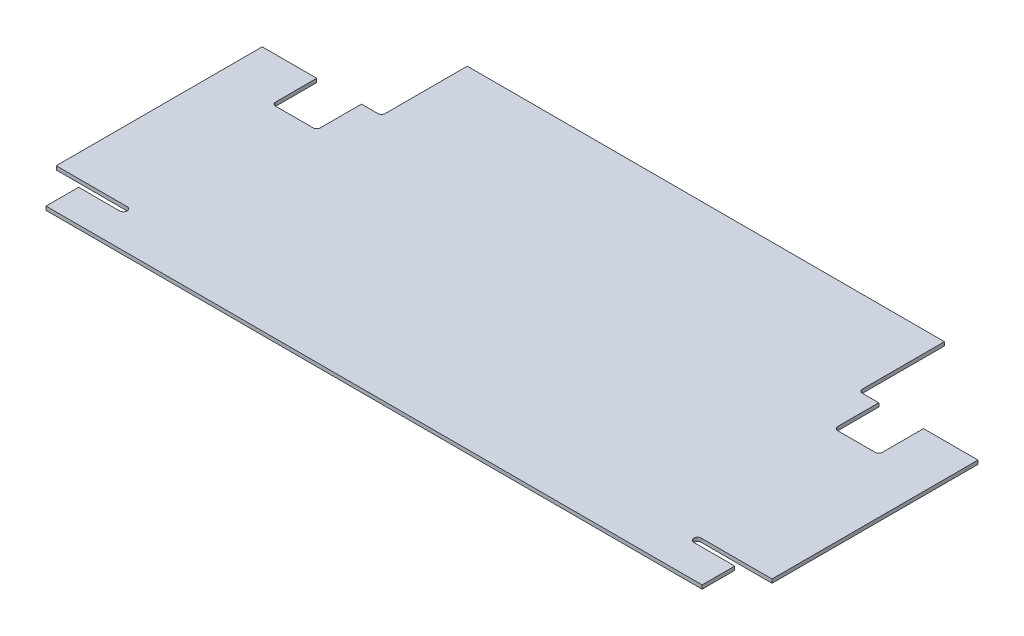
SolidWorks part; units mm, degrees
material "Acrylic (Medium-high impact)"
ref_plane "Front Plane" through (0, 0, 0) normal (0, 0, 1) x (1, 0, 0)
ref_plane "Top Plane" through (0, 0, 0) normal (0, 1, 0) x (1, 0, 0)
ref_plane "Right Plane" through (0, 0, 0) normal (1, 0, 0) x (0, 0, -1)
sketch "Sketch1" plane through (0, 0, 0) normal (0, 1, 0) x (1, 0, 0)
  line L1 (-304.8, 152.4) -> (304.8, 152.4)
  line L2 (-304.8, 152.4) -> (-304.8, -152.4)
  line L3 (-304.8, -152.4) -> (304.8, -152.4)
  line L4 (304.8, 152.4) -> (304.8, -152.4)
  line L5 (-304.8, 152.4) -> (304.8, -152.4) construction
  line L6 (-304.8, -152.4) -> (304.8, 152.4) construction
  point P0 (0, 0)
  dimension "D1" = 609.6
  dimension "D2" = 304.8
extrude "Boss-Extrude1" add sketch "Sketch1" along normal blind 3.175
sketch "Sketch3" plane through (0, 3.175, 0) normal (0, 1, 0) x (1, 0, 0)
  line L0 (-304.8, -152.4) -> (304.8, -152.4) construction
  line L1 (-304.8, 152.4) -> (304.8, 152.4)
  line L2 (-304.8, 152.4) -> (-304.8, 57.15)
  line L3 (-304.8, 57.15) -> (-203.2, 57.15)
  line L4 (-203.2, 130.175) -> (-203.2, 57.15)
  line L5 (0, 38.7483) -> (0, -39.3783) construction
  line L6 (203.2, 130.175) -> (203.2, 57.15)
  line L7 (304.8, 57.15) -> (203.2, 57.15)
  line L8 (304.8, 152.4) -> (304.8, 57.15)
  line L10 (-203.2, 130.175) -> (203.2, 130.175)
  dimension "D1" = 101.6
  dimension "D2" = 209.55
  dimension "D3" = 282.575
extrude "Cut-Extrude1" cut sketch "Sketch3" against normal up to next
fillet "Fillet1" radius 3.175 2 edges at (203.2, 1.5875, -57.15) (-203.2, 1.5875, -57.15)
sketch "Sketch4" plane through (0, 3.175, 0) normal (0, 1, 0) x (1, 0, 0)
  line L0 (206.375, 57.15) -> (304.8, 57.15) construction
  line L1 (220.2815, 57.15) -> (258.3815, 57.15)
  line L2 (220.2815, 57.15) -> (220.2815, 19.05)
  line L3 (220.2815, 19.05) -> (258.3815, 19.05)
  line L4 (258.3815, 57.15) -> (258.3815, 19.05)
  line L5 (220.2815, 57.15) -> (258.3815, 19.05) construction
  line L6 (220.2815, 19.05) -> (258.3815, 57.15) construction
  line L7 (304.8, -152.4) -> (304.8, 57.15) construction
  point P0 (239.3315, 38.1)
  dimension "D1" = 38.1
  dimension "D2" = 65.4685
  dimension "D3" = 38.1
extrude "Cut-Extrude2" cut sketch "Sketch4" against normal up to next
fillet "Fillet2" radius 3.175 2 edges at (258.3815, 1.5875, -19.05) (220.2815, 1.5875, -19.05)
mirror "Mirror1" about plane through (0, 0, 0) normal (1, 0, 0) of "Fillet2", "Cut-Extrude2"
sketch "Sketch5" plane through (0, 3.175, 0) normal (0, 1, 0) x (1, 0, 0)
  line L0 (-279.4, -152.4) -> (-279.4, -124.6187)
  line L1 (-304.8, -152.4) -> (-279.4, -152.4)
  line L2 (-304.8, -152.4) -> (-304.8, -118.2687)
  line L3 (-304.8, -118.2687) -> (-241.3, -118.2687)
  line L4 (-279.4, -124.6187) -> (-241.3, -124.6187)
  line L5 (-241.3, -124.6187) -> (-241.3, -118.2687)
  line L6 (-241.3, -121.4437) -> (-334.5415, -121.4437) construction
  dimension "D1" = 30.9562
  dimension "D2" = 25.4
  dimension "D3" = 38.1
  dimension "D4" = 6.35
extrude "Cut-Extrude3" cut sketch "Sketch5" against normal up to next
fillet "Fillet3" radius 3.175 2 edges at (-241.3, 1.5875, 124.6187) (-241.3, 1.5875, 118.2687)
mirror "Mirror2" about plane through (0, 0, 0) normal (1, 0, 0) of "Fillet3", "Cut-Extrude3"
